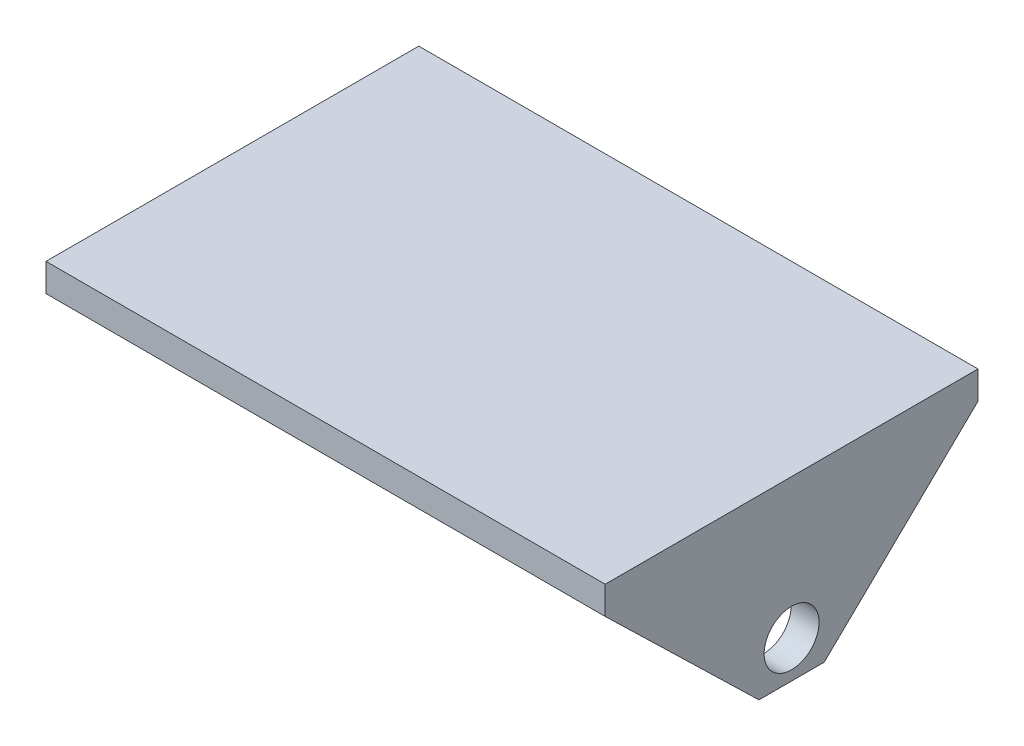
SolidWorks part; units mm, degrees
ref_plane "Front Plane" through (0, 0, 0) normal (0, 0, 1) x (1, 0, 0)
ref_plane "Top Plane" through (0, 0, 0) normal (0, 1, 0) x (1, 0, 0)
ref_plane "Right Plane" through (0, 0, 0) normal (1, 0, 0) x (0, 0, -1)
sketch "Sketch1" plane through (0, 0, 0) normal (0, 1, 0) x (1, 0, 0)
  line L1 (-30, 20) -> (30, 20)
  line L2 (-30, 20) -> (-30, -20)
  line L3 (-30, -20) -> (30, -20)
  line L4 (30, 20) -> (30, -20)
  line L5 (-30, 20) -> (30, -20) construction
  line L6 (-30, -20) -> (30, 20) construction
  point P0 (0, 0)
  dimension "D1" = 60
  dimension "D2" = 40
extrude "Boss-Extrude1" add sketch "Sketch1" along normal blind 3
sketch "Sketch2" plane through (30, 0, 0) normal (1, 0, 0) x (0, 0, -1)
  line L0 (-20, 3) -> (20, 3)
  line L1 (-20, 3) -> (-20, -16)
  line L2 (20, 3) -> (20, -16) construction
  line L3 (-20, -16) -> (20, -16)
  line L4 (-20, 3) -> (20, -16) construction
  line L5 (20, 3) -> (-20, -16) construction
  line L6 (-3.5, -16) -> (3.5, -16)
  line L7 (3.5, -16) -> (20, 0)
  line L8 (20, 0) -> (20, 3)
  line L9 (-20, 3) -> (-20, 0)
  line L10 (-20, 0) -> (-3.5, -16)
  line L11 (0, -16) -> (0, -12) construction
  circle A0 centre (0, -12) radius 2.95
  point P6 (0, -6.5)
  point P10 (0, -16)
  line M11 (-20, 0) -> (20, 0)
  dimension "D1" = 19
extrude "Boss-Extrude2" add sketch "Sketch2" against normal blind 3 contours L10 L3 L7 A0 M11 region at (30, -5.6672, 0)
ref_plane "Plane1" through (0, 0, 0) normal (-1, 0, 0) x (0, 0, 1)
mirror "Mirror1" about plane through (0, 0, 0) normal (-1, 0, 0) of "Boss-Extrude2"
